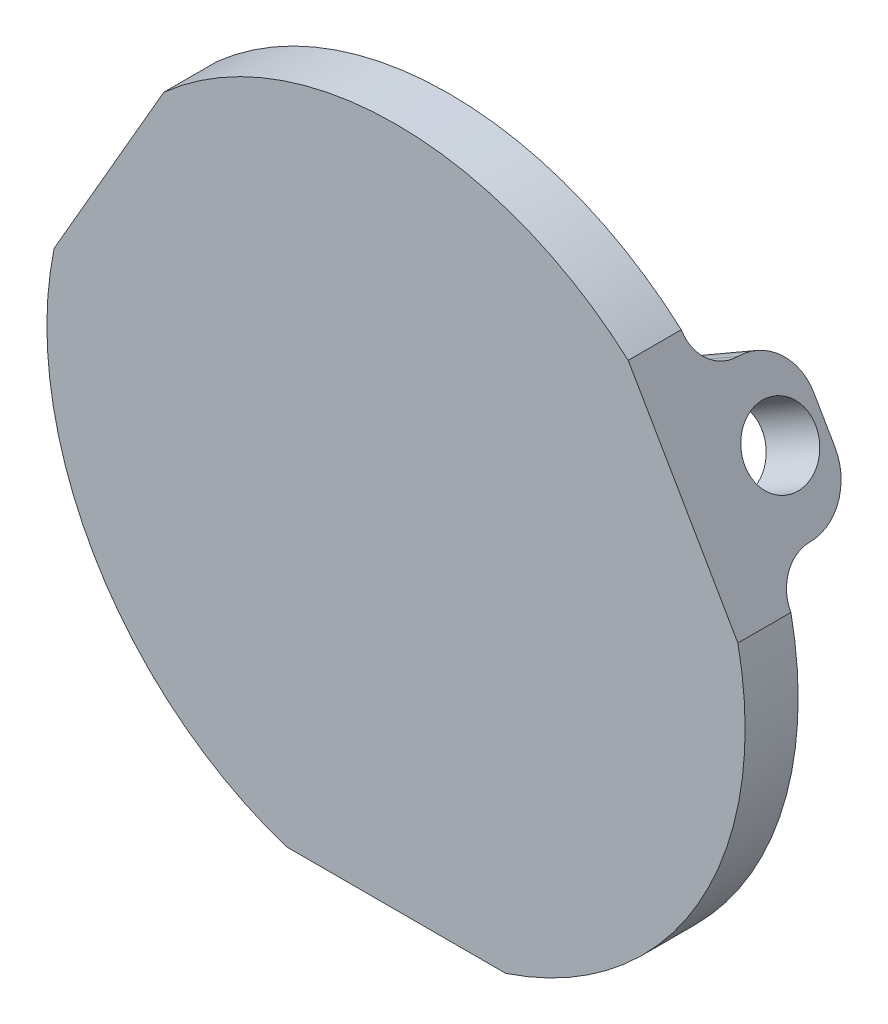
SolidWorks part; units mm, degrees
note: The reader was unsure of these and kept them because the rebuilt part matched: shared geometry of "Sketch2<3>", "Sketch2<4>".
ref_plane "Front Plane" through (0, 0, 0) normal (0, 0, 1) x (1, 0, 0)
ref_plane "Top Plane" through (0, 0, 0) normal (0, 1, 0) x (1, 0, 0)
ref_plane "Right Plane" through (0, 0, 0) normal (1, 0, 0) x (0, 0, -1)
sketch "Sketch2" plane through (0, 0, 0) normal (0, 0, 1) x (1, 0, 0)
  line L1 (-24.8193, -89) -> (24.8193, -89)
  line L2 (-24.8193, -89) -> (-24.8193, -75)
  line L3 (-24.8193, -75) -> (24.8193, -75)
  line L4 (24.8193, -89) -> (24.8193, -75)
  line L5 (-24.8193, -75) -> (24.8193, -75)
  line L6 (-24.8193, -75) -> (-24.8193, -61)
  line L7 (-24.8193, -61) -> (24.8193, -61)
  line L8 (24.8193, -75) -> (24.8193, -61)
  circle A0 centre (0, 0) radius 79
  point P7 (28.8814, -52.6137)
  point P8 (24.8193, -68)
  dimension "D1" = 158
  dimension "D2" = 75
  dimension "D3" = 14
extrude "Boss-Extrude1" add sketch "Sketch2" along normal blind 12 contours A0
extrude "Cut-Extrude1" cut sketch "Sketch2<3>" against normal through all both and the other way through all contours L2 L1 L4 L3
sketch "Sketch2<3>" plane through (0, 0, 0) normal (0, 0, 1) x (1, 0, 0) same geometry as "Sketch2"
extrude "Boss-Extrude2" add sketch "Sketch2<4>" against normal blind 20 contours L3 L8 L7 L6
sketch "Sketch2<4>" plane through (0, 0, 0) normal (0, 0, 1) x (1, 0, 0) same geometry as "Sketch2"
sketch "Sketch3" plane through (0, -75, 0) normal (0, -1, 0) x (1, 0, 0)
  line L0 (-24.8193, -20) -> (24.8193, -20) construction
  line L1 (-79, 0) -> (79, 0) construction
  line L2 (-24.8193, -20) -> (-24.8193, 0) construction
  line L3 (-16.3018, -8.5176) -> (-16.3018, 6.2859) construction
  line L4 (-24.8193, 0) -> (-24.8193, -20)
  line L5 (-24.8193, -20) -> (-4.8193, -20)
  circle A0 centre (0, -10) radius 8
  arc A1 (-24.8193, 0) -> (-16.3018, -8.5176) centre (-24.8193, -8.5176) cw
  arc A2 (-16.3018, -8.5176) -> (-4.8193, -20) centre (-4.8193, -8.5176) ccw
  dimension "D1" = 16
  dimension "D2" = 10
extrude "Cut-Extrude2" cut sketch "Sketch3" against normal through all both and the other way through all
mirror "Mirror1" about plane through (0, 0, 0) normal (1, 0, 0) of "Cut-Extrude2"
pattern_circular "CirPattern1" count 3 over 360 about axis through (0, 0, 0) along (0, 0, 1) of "Cut-Extrude1", "Boss-Extrude2", "Cut-Extrude2", "Mirror1"
move or copy body "Body-Move/Copy1" parameters "D1"=0, "D2"=0, "D3"=10
